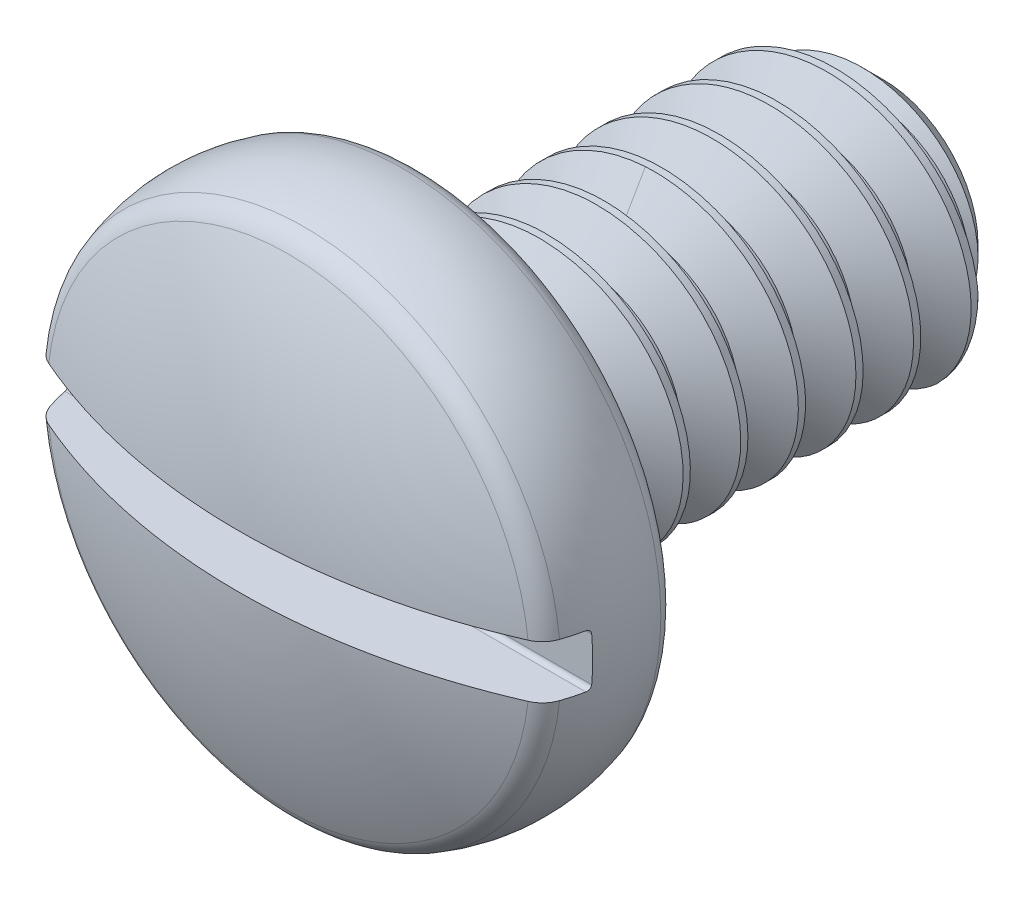
SolidWorks part; units mm, degrees
ref_plane "Front Plane" through (0, 0, 0) normal (0, 0, 1) x (1, 0, 0)
ref_plane "Top Plane" through (0, 0, 0) normal (0, 1, 0) x (1, 0, 0)
ref_plane "Right Plane" through (0, 0, 0) normal (1, 0, 0) x (0, 0, -1)
sketch "Sketch1" plane through (0, 0, 0) normal (1, 0, 0) x (0, 0, -1)
  line L0 (-1.4, 0) -> (1.4, 0) construction
  line L1 (-0.6, 1.15) -> (-0.6, -1.15) construction
  line L3 (1.4, 0.6) -> (1.4, -0.6) construction
  line L4 (1.3844, 0.6271) -> (1.5094, 0.4106) construction
  line L5 (1.5094, 0.4106) -> (1.6344, 0.6271) construction
  line L6 (1.6344, 0.6271) -> (1.3844, 0.6271) construction
  line L7 (1.5094, 0.6271) -> (1.5094, 0.6) construction
  line L8 (1.5094, 0.4106) -> (1.5094, 0.4376) construction
  line L9 (1.4937, 0.4376) -> (1.525, 0.4376)
  line L11 (-0.6, 1.15) -> (-1.16, 1.15) construction
  point P5 (-0.6, 0)
  point P10 (0.525, -0.6)
  dimension "Head Diameter" = 2.3
  dimension "Thread Size" = 1.2
  dimension "Length" = 2
  dimension "Thread Note" = 0.875
  dimension "Pitch" = 0.25
  dimension "Pitch/8" = 0.0312
  dimension "Approx Head Edge Flat" = 0.56
  dimension "Head Height" = 0.8
sketch "Sketch2" plane through (0, 0, 0) normal (1, 0, 0) x (0, 0, -1)
  line L0 (-0.6, 1.15) -> (-1.16, 1.15) construction
  line L1 (-1.16, 1.0925) -> (-0.6, 1.0925) construction
  line L2 (-0.6, 1.0925) -> (-0.6, 0.612)
  line L3 (-1.4, 0) -> (-1.4, 1.0925) construction
  line L4 (-0.5, 0.6) -> (1.2125, 0.6)
  line L5 (1.4, 0.4125) -> (1.4, 0)
  line L8 (1.4, 0) -> (-1.4, 0)
  line L9 (1.2125, 0.6) -> (1.4, 0.4125)
  line L10 (1.2125, -0.6) -> (1.2125, 0.6) construction
  line L11 (-0.6, 0.612) -> (-0.5, 0.612)
  line L12 (-0.5, 0.612) -> (-0.5, 0.6)
  line L14 (-1.4, 0) -> (1.4, 0) construction
  line L15 (-0.6, 1.15) -> (-0.6, -1.15) construction
  arc A0 (-1.4, 0) -> (-1.16, 1.0925) centre (1.2066, 0) cw
  arc A1 (-1.16, 1.0925) -> (-0.6, 1.0925) centre (-0.88, 0.4395) cw
  point P13 (1.4, 0.6)
  point P25 (1.2125, 0)
  dimension "D1" = 0.1875
  dimension "D2" = 45
  dimension "D3" = 0.612
  dimension "D4" = 0.1
  dimension "D5" = 0.0575
revolve "Revolve1" add sketch "Sketch2" angle 360 about L0
sketch "Sketch9" plane through (0, 0, 0) normal (1, 0, 0) x (0, 0, -1)
  line L1 (-1.4, 0.115) -> (-1, 0.115)
  line L2 (-1.4, 0.115) -> (-1.4, -0.115)
  line L3 (-1.4, -0.115) -> (-1, -0.115)
  line L4 (-1, 0.115) -> (-1, -0.115)
  dimension "D1" = 0.23
  dimension "D2" = 0.4
extrude "Cut-Extrude1" cut sketch "Sketch9" against normal through all both and the other way through all
fillet "Fillet1" radius 0.02 2 edges at (0, 0.115, 1) (0, -0.115, 1)
fillet "Fillet2" radius 0.12 3 edges at (1.0925, 0, 0.6) (0, -1.0925, 1.16) (0, 1.0925, 1.16)
chamfer "Chamfer1" distance 0.033 angle 45 1 edges at (0.612, 0, 0.6)
sketch "Drawing1" plane through (0, 0, 0) normal (0, 0, 1) x (1, 0, 0)
  circle A0 centre (0, 0) radius 1.15 construction
sketch "Sketch6" plane through (0, 0, -1.4) normal (0, 0, -1) x (-1, 0, 0)
  circle A0 centre (0, 0) radius 0.6
split "Split1" bodies to split 110 resulting bodies 111 112 split by face at (0.612, 0, 0.5)
curve "Helix/Spiral1" pitch 0.25 height 1.25 radius 0.6 centre (0, 0, -1.4) axis (0, 0, 1) start towards (0, 1, 0)
sketch "Sketch7" plane through (0, 0, 0) normal (1, 0, 0) x (0, 0, -1)
  line L0 (1.4, 0.6) -> (1.6187, 0.6)
  line L1 (1.6187, 0.6) -> (1.525, 0.4376)
  line L2 (1.4937, 0.4376) -> (1.525, 0.4376)
  line L3 (1.4937, 0.4376) -> (1.4, 0.6)
  line L4 (1.5094, 0.4106) -> (1.6344, 0.6271) construction
sweep "Cut-Sweep1" cut profiles "Sketch7" path "Helix/Spiral1" align with end faces yes
pattern_linear "LPattern1" count 3 spacing 0.75 along (0, 0, 1) of "Cut-Sweep1"
sketch "Sketch8" plane through (0, 0, 0.5) normal (0, 0, -1) x (-1, 0, 0)
  circle A0 centre (0, 0) radius 0.612
  circle A1 centre (0, 0) radius 0.6 construction
  circle A2 centre (0, 0) radius 0.612 construction
extrude "Boss-Extrude1" add sketch "Sketch8" along normal through all draft 45
equation "\"Pitch/8@Sketch1\" = \"Pitch@Sketch1\" * .125"
equation "\"Thread Note@Sketch1\" = \"Pitch@Sketch1\" * 3.5"
equation "\"Approx Head Edge Flat@Sketch1\"=\"Head Height@Sketch1\"*.7"
equation "\"D1@Sketch2\"=\"Pitch@Sketch1\"*.750"
equation "\"D4@Helix/Spiral1\"=\"Pitch@Sketch1\""
equation "\"D3@Sketch2\"=\"Thread Size@Sketch1\"*.51"
equation "\"D4@Sketch2\"=\"Length@Sketch1\"*.05"
equation "\"D1@Fillet1\"=\"Head Height@Sketch1\" * .025"
equation "\"D1@Sketch9\"=\"Head Diameter@Sketch1\"*.1"
equation "\"D5@Sketch2\"=\"Head Diameter@Sketch1\"*.025"
equation "\"D1@Fillet2\"=\"Head Height@Sketch1\" * .15"
equation "\"D1@Chamfer1\"=\"D4@Sketch2\"*.33"
equation "\"D2@Sketch9\" = \"Head Height@Sketch1\" * .5"
equation "\"Thread Count\"= \"Length@Sketch1\" * 0.4 / \"Pitch@Sketch1\""
equation "\"Rounded Thread Count\"= IIF ( \"Thread Count\" - int ( \"Thread Count\" ) > 0 , int ( \"Thread Count\" ) + 1 , \"Thread Count\" )"
equation "\"Segment Length\"= \"Pitch@Sketch1\" * \"Rounded Thread Count\""
equation "\"D3@LPattern1\"=\"Segment Length\" - \"Pitch@Sketch1\""
equation "\"D3@Helix/Spiral1\"=\"Segment Length\" + \"Pitch@Sketch1\""
